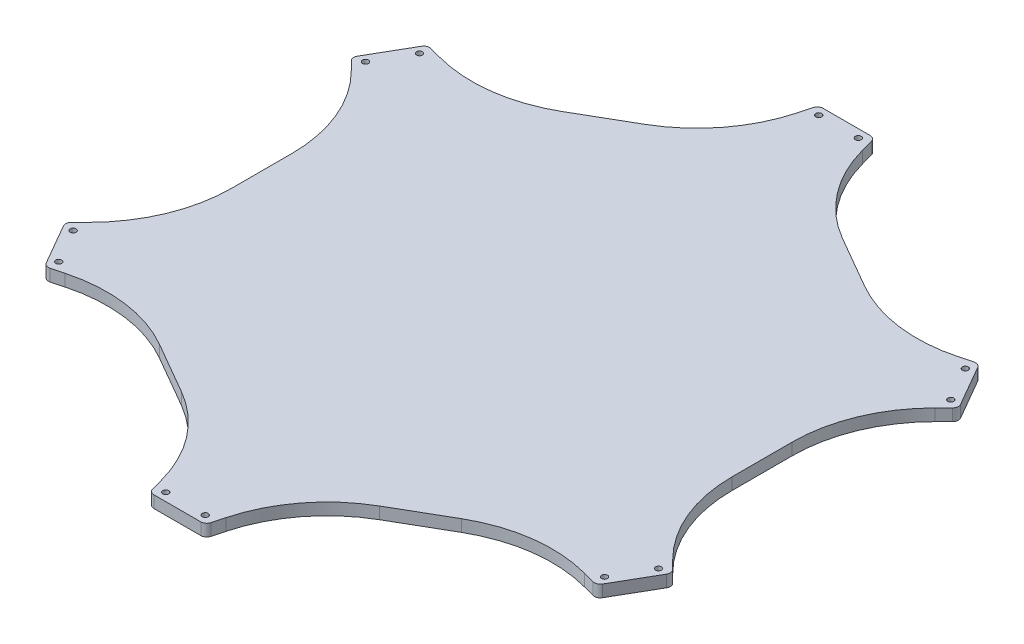
SolidWorks part; units mm, degrees
ref_plane "Front Plane" through (0, 0, 0) normal (0, 0, 1) x (1, 0, 0)
ref_plane "Top Plane" through (0, 0, 0) normal (0, 1, 0) x (1, 0, 0)
ref_plane "Right Plane" through (0, 0, 0) normal (1, 0, 0) x (0, 0, -1)
sketch "Sketch1" plane through (0, 0, 0) normal (0, 1, 0) x (1, 0, 0)
  line L1 (-81.1177, 140.5) -> (-162.2354, 0)
  line L2 (-162.2354, 0) -> (-81.1177, -140.5)
  line L3 (-81.1177, -140.5) -> (81.1177, -140.5)
  line L4 (81.1177, -140.5) -> (162.2354, 0)
  line L5 (162.2354, 0) -> (81.1177, 140.5)
  line L6 (81.1177, 140.5) -> (-81.1177, 140.5)
  circle A0 centre (0, 0) radius 140.5 construction
  dimension "D1" = 281
extrude "Boss-Extrude1" add sketch "Sketch1" along normal blind 5
sketch "Sketch3" plane through (0, 5, 0) normal (0, 1, 0) x (1, 0, 0)
  line L0 (0, 0) -> (0, 140.5) construction
  line L1 (81.1177, 140.5) -> (-81.1177, 140.5) construction
  line L2 (-11.75, 140.5) -> (11.75, 140.5) construction
  line L3 (0, 0) -> (121.6766, 70.25) construction
  line L4 (162.2354, 0) -> (81.1177, 140.5) construction
  line L5 (115.8016, 80.4258) -> (127.5516, 60.0742) construction
  line L6 (11.75, 140.5) -> (20.0127, 109.6631)
  line L7 (20.0127, 109.6631) -> (84.9646, 72.1631)
  line L8 (84.9646, 72.1631) -> (115.8016, 80.4258)
  line L9 (11.75, 140.5) -> (81.1177, 140.5)
  line L10 (81.1177, 140.5) -> (115.8016, 80.4258)
  line L11 (11.75, 140.5) -> (115.8016, 80.4258) construction
  line L12 (-8.3, 137.1) -> (8.3, 137.1) construction
  circle A0 centre (8.3, 137.1) radius 1.25
  circle A1 centre (-8.3, 137.1) radius 1.25
  point P7 (0, 140.5)
  point P13 (121.6766, 70.25)
  point P27 (0, 137.1)
  dimension "D4" = 2.5
  dimension "D1" = 23.5
  dimension "D2" = 23.5
  dimension "D3" = 75
  dimension "D5" = 3.4
  dimension "D7" = 16.6
extrude "Cut-Extrude1" cut sketch "Sketch3" against normal through all
ref_axis "Axis1" through (0, 0, 0) along (0, 1, 0)
pattern_circular "CirPattern2" count 6 over 360 about axis through (0, 0, 0) along (0, 1, 0) of "Cut-Extrude1"
fillet "Fillet3" radius 2.5 12 edges at (115.8016, 2.5, -80.4258) (11.75, 2.5, -140.5) (127.5516, 2.5, -60.0742) (127.5516, 2.5, 60.0742) (115.8016, 2.5, 80.4258) (11.75, 2.5, 140.5) (-11.75, 2.5, 140.5) (-115.8016, 2.5, 80.4258) (-127.5516, 2.5, 60.0742) (-127.5516, 2.5, -60.0742) (-115.8016, 2.5, -80.4258) (-11.75, 2.5, -140.5)
fillet "Fillet4" radius 60 12 edges at (84.9646, 2.5, -72.1631) (20.0127, 2.5, -109.6631) (-20.0127, 2.5, -109.6631) (-84.9646, 2.5, -72.1631) (-104.9774, 2.5, -37.5) (-104.9774, 2.5, 37.5) (-84.9646, 2.5, 72.1631) (-20.0127, 2.5, 109.6631) (20.0127, 2.5, 109.6631) (84.9646, 2.5, 72.1631) (104.9774, 2.5, 37.5) (104.9774, 2.5, -37.5)
